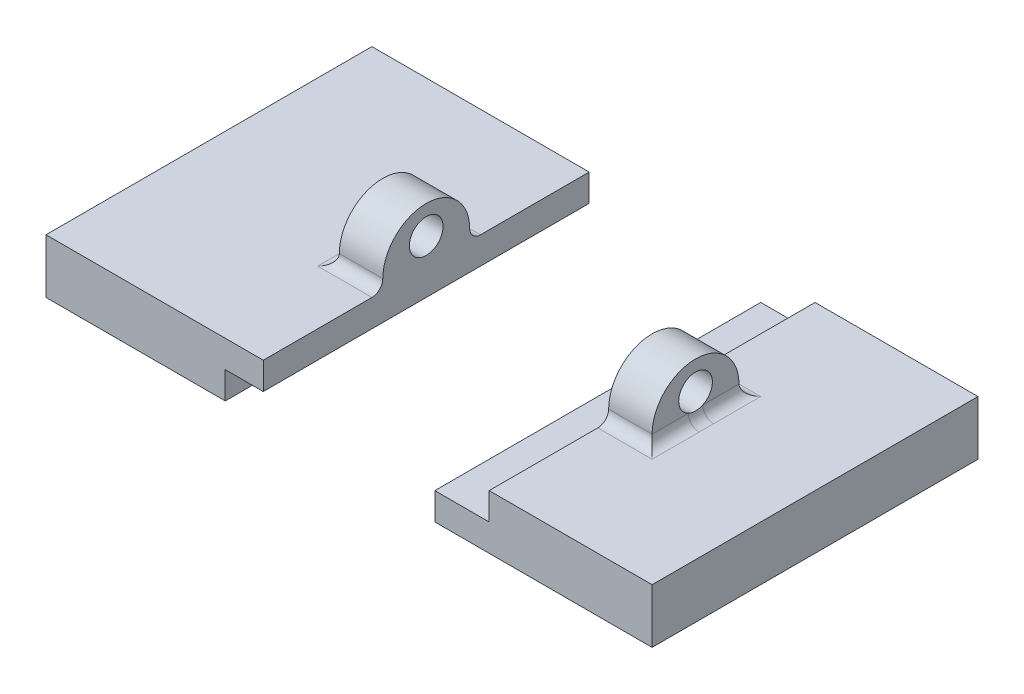
SolidWorks part; units mm, degrees
ref_plane "Front Plane" through (0, 0, 0) normal (0, 0, 1) x (1, 0, 0)
ref_plane "Top Plane" through (0, 0, 0) normal (0, 1, 0) x (1, 0, 0)
ref_plane "Right Plane" through (0, 0, 0) normal (1, 0, 0) x (0, 0, -1)
sketch "Sketch1" plane through (0, 0, 0) normal (0, 1, 0) x (1, 0, 0)
  line L1 (0, 0) -> (-20, 0)
  line L2 (0, 0) -> (0, 30)
  line L3 (0, 30) -> (-20, 30)
  line L4 (-20, 0) -> (-20, 30)
  line L5 (15.7913, 0) -> (35.7913, 0)
  line L6 (15.7913, 0) -> (15.7913, 30)
  line L7 (15.7913, 30) -> (35.7913, 30)
  line L8 (35.7913, 0) -> (35.7913, 30)
  dimension "D1" = 20
  dimension "D2" = 30
  dimension "D3" = 30
  dimension "D4" = 20
extrude "Boss-Extrude1" add sketch "Sketch1" along normal blind 5
sketch "Sketch2" plane through (0, 0, 0) normal (1, 0, 0) x (0, 0, -1)
  line L0 (0, 5) -> (0, 0) construction
  line L1 (30, 0) -> (0, 0)
  line L2 (30, 0) -> (30, 2.5)
  line L3 (30, 2.5) -> (0, 2.5)
  line L4 (0, 0) -> (0, 2.5)
extrude "Cut-Extrude1" cut sketch "Sketch2" against normal blind 3.5
sketch "Sketch3" plane through (15.7913, 0, 0) normal (-1, 0, 0) x (0, 0, 1)
  line L0 (0, 5) -> (0, 0) construction
  line L1 (-30, 5) -> (0, 5)
  line L2 (-30, 5) -> (-30, 2.5)
  line L3 (-30, 2.5) -> (0, 2.5)
  line L4 (0, 5) -> (0, 2.5)
extrude "Cut-Extrude2" cut sketch "Sketch3" against normal blind 5
sketch "Sketch4" plane through (20.7913, 0, 0) normal (-1, 0, 0) x (0, 0, 1)
  line L0 (0, 5) -> (-30, 5) construction
  line L1 (-19, 5) -> (-11, 5)
  line L2 (-19, 5) -> (-19, 6)
  line L4 (-11, 5) -> (-11, 6)
  line L5 (-30, 5) -> (-30, 2.5) construction
  line L6 (0, 2.5) -> (0, 5) construction
  arc A0 (-11, 6) -> (-19, 6) centre (-15, 6) ccw
  circle A1 centre (-15, 7.4) radius 1.55
  point P13 (0, 0)
  point P14 (0, 0)
  point P17 (-14.798, 5)
  dimension "D4" = 3.1
  dimension "D1" = 1
  dimension "D2" = 11
  dimension "D3" = 11
  dimension "D5" = 4
  dimension "D6" = 2.4
extrude "Boss-Extrude2" add sketch "Sketch4" against normal blind 4
fillet "Fillet1" radius 1 3 edges at (22.7913, 5, -19) (24.7913, 5, -15) (22.7913, 5, -11)
sketch "Sketch5" plane through (0, 0, 0) normal (1, 0, 0) x (0, 0, -1)
  line L0 (0, 5) -> (30, 5) construction
  line L1 (11, 5) -> (19, 5)
  line L2 (11, 5) -> (11, 6)
  line L4 (19, 5) -> (19, 6)
  line L5 (30, 5) -> (30, 2.5) construction
  line L6 (0, 5) -> (0, 2.5) construction
  arc A0 (19, 6) -> (11, 6) centre (15, 6) ccw
  circle A1 centre (15, 7.4) radius 1.55
  dimension "D4" = 3.1
  dimension "D6" = 2.4
  dimension "D1" = 1
  dimension "D2" = 11
  dimension "D3" = 11
  dimension "D5" = 4
extrude "Boss-Extrude3" add sketch "Sketch5" against normal blind 4
fillet "Fillet2" radius 1 3 edges at (-2, 5, -11) (-4, 5, -15) (-2, 5, -19)
